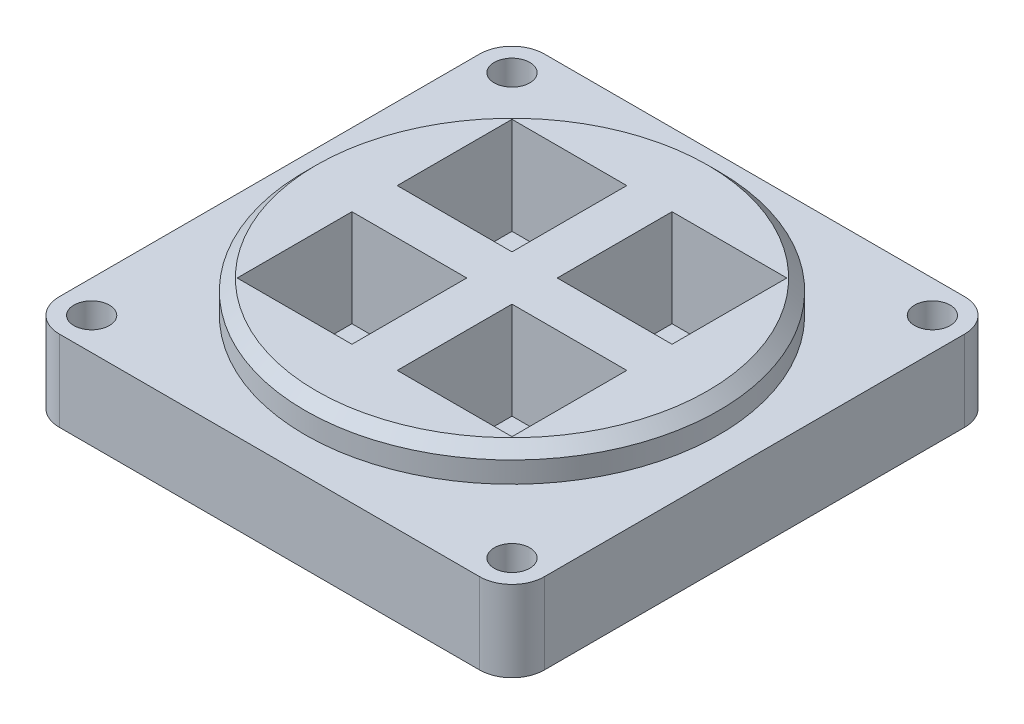
SolidWorks part; units mm, degrees
ref_plane "Front Plane" through (0, 0, 0) normal (0, 0, 1) x (1, 0, 0)
ref_plane "Top Plane" through (0, 0, 0) normal (0, 1, 0) x (1, 0, 0)
ref_plane "Right Plane" through (0, 0, 0) normal (1, 0, 0) x (0, 0, -1)
sketch "Sketch1" plane through (0, 0, 0) normal (0, 1, 0) x (1, 0, 0)
  line L1 (-38.1, -38.1) -> (38.1, -38.1)
  line L2 (-38.1, -38.1) -> (-38.1, 38.1)
  line L3 (-38.1, 38.1) -> (38.1, 38.1)
  line L4 (38.1, -38.1) -> (38.1, 38.1)
  line L5 (-38.1, -38.1) -> (38.1, 38.1) construction
  line L6 (-38.1, 38.1) -> (38.1, -38.1) construction
  point P0 (0, 0)
  dimension "D1" = 76.2
  dimension "D2" = 76.2
extrude "Boss-Extrude1" add sketch "Sketch1" along normal blind 12.7
sketch "Sketch2" plane through (0, 12.7, 0) normal (0, 1, 0) x (1, 0, 0)
  line L0 (38.1, -38.1) -> (38.1, 38.1) construction
  line L1 (0, 0) -> (38.1, 38.1) construction
  circle A0 centre (0, 0) radius 38.1 construction
  circle A1 centre (0, 0) radius 32.512
  circle A2 centre (33.02, 33.02) radius 2.794
  circle A3 centre (33.02, -33.02) radius 2.794
  circle A4 centre (-33.02, -33.02) radius 2.794
  circle A5 centre (-33.02, 33.02) radius 2.794
  circle A6 centre (-33.02, 33.02) radius 5.08
  circle A7 centre (33.02, 33.02) radius 5.08
  circle A8 centre (33.02, -33.02) radius 5.08
  circle A9 centre (-33.02, -33.02) radius 5.08
  point P20 (0, 0)
  point P28 (0, 0)
  dimension "D2" = 5.588
  dimension "D3" = 5.08
  dimension "D4" = 4
  dimension "D5" = 10.16
  dimension "D1" = 5.588
  dimension "D6" = 4
extrude "Cut-Extrude1" cut sketch "Sketch2" against normal through all contours A3 | A2 | A4 | A5
extrude "Boss-Extrude2" add sketch "Sketch2<3>" along normal blind 5.08 contours A1
sketch "Sketch2<3>" plane through (0, 12.7, 0) normal (0, 1, 0) x (1, 0, 0) same geometry as "Sketch2"
sketch "Sketch5" plane through (0, 17.78, 0) normal (0, 1, 0) x (1, 0, 0)
  line L0 (-3.5554, 21.5894) -> (-21.5894, 3.5554) construction
  line L5 (-3.5554, 21.5894) -> (-3.5554, 3.5554)
  line L6 (-21.5894, 21.5894) -> (-3.5554, 3.5554) construction
  line L7 (-38.1, 38.1) -> (0, 0) construction
  line L8 (21.5894, 3.5554) -> (3.5554, 3.5554)
  line L9 (-3.5554, 3.5554) -> (-21.5894, 3.5554)
  line L10 (-21.5894, 3.5554) -> (-21.5894, 21.5894)
  line L11 (-21.5894, 21.5894) -> (-3.5554, 21.5894)
  line L12 (21.5894, 21.5894) -> (21.5894, 3.5554)
  line L13 (3.5554, 21.5894) -> (21.5894, 21.5894)
  line L14 (3.5554, 3.5554) -> (3.5554, 21.5894)
  line L15 (3.5554, -21.5894) -> (3.5554, -3.5554)
  line L16 (21.5894, -21.5894) -> (3.5554, -21.5894)
  line L17 (21.5894, -3.5554) -> (21.5894, -21.5894)
  line L18 (3.5554, -3.5554) -> (21.5894, -3.5554)
  line L19 (-21.5894, -3.5554) -> (-3.5554, -3.5554)
  line L20 (-21.5894, -21.5894) -> (-21.5894, -3.5554)
  line L21 (-3.5554, -21.5894) -> (-21.5894, -21.5894)
  line L22 (-3.5554, -3.5554) -> (-3.5554, -21.5894)
  circle A0 centre (0, 0) radius 32.512 construction
  point P6 (-12.5724, 12.5724)
  point P26 (0, 0)
  point P39 (0, 0)
  dimension "D1" = 18.034
  dimension "D2" = 18.034
  dimension "D3" = 17.78
  dimension "D4" = 4
extrude "Cut-Extrude2" cut sketch "Sketch5" against normal blind 15.24 contours L19 L22 L21 L20 | L11 L5 L9 L10 | L8 L14 L13 L12 | L15 L18 L17 L16
fillet "Fillet1" radius 5.08 4 edges at (-38.1, 6.35, 38.1) (38.1, 6.35, 38.1) (38.1, 6.35, -38.1) (-38.1, 6.35, -38.1)
chamfer "Chamfer1" distance 1.778 angle 45 1 edges at (0, 17.78, 32.512)
